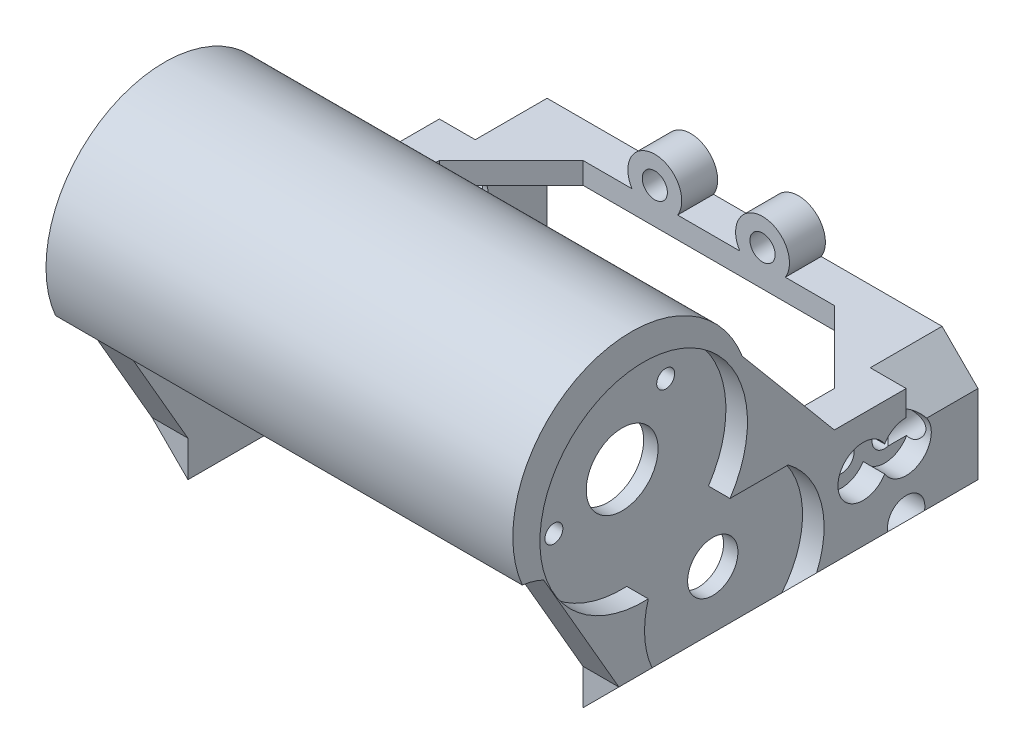
SolidWorks part; units mm, degrees
ref_plane "Front Plane" through (0, 0, 0) normal (0, 0, 1) x (1, 0, 0)
ref_plane "Top Plane" through (0, 0, 0) normal (0, 1, 0) x (1, 0, 0)
ref_plane "Right Plane" through (0, 0, 0) normal (1, 0, 0) x (0, 0, -1)
sketch "Sketch1" plane through (0, 0, 0) normal (1, 0, 0) x (0, 0, -1)
  line L0 (0, 0) -> (-11.1847, 15.9735) construction
  line L1 (0, 0) -> (24.1879, 0) construction
  line L3 (-3.4511, -28.0225) -> (46.5489, -28.0225)
  line L4 (46.5489, -28.0225) -> (46.5489, -7.0225)
  line L5 (26.5489, -7.0225) -> (46.5489, -7.0225)
  line L6 (-3.4511, -28.0225) -> (-3.4511, -23.0225)
  line L8 (6.0612, 7.9064) -> (-9.5027, -2.9915) construction
  line L9 (0, 0) -> (15.5119, -22.1533) construction
  line L10 (-3.4511, -23.0225) -> (-13.9311, -4.8707)
  line L11 (26.5489, -7.0225) -> (13.7066, 8.3096)
  line L12 (-3.4511, -23.0225) -> (-21.8299, -23.0225) construction
  arc A2 (-4.3527, -13.8313) -> (14.4859, -0.6404) centre (-1.7207, 2.4575) ccw construction
  circle A3 centre (0, 0) radius 5
  circle A4 centre (0, 0) radius 14.5 construction
  arc A6 (13.7066, 8.3096) -> (-16.9046, -4) centre (-1.7207, 2.4575) ccw
  circle A7 centre (6.0612, 7.9064) radius 1.25
  circle A8 centre (-9.5027, -2.9915) radius 1.25
  circle A9 centre (12.6187, -18.0213) radius 3.5
  circle A10 centre (36.5489, -14.0225) radius 1.75
  circle A11 centre (30.5489, -14.0225) radius 1.75
  circle A12 centre (36.5489, -22.5225) radius 2.6
  arc A13 (-16.9046, -4) -> (-13.9311, -4.8707) centre (-18.1939, -13.9165) cw
  point P13 (-15.6278, -4.8647)
  point P24 (-1.7207, 2.4575)
  point P32 (-15.9486, -4.3678)
  point P33 (-16.0428, -4.0182)
  dimension "D1" = 20
  dimension "D2" = 2.5
  dimension "D3" = 33
  dimension "D9" = 10
  dimension "D10" = 29
  dimension "D13" = 10
  dimension "D16" = 2.5
  dimension "D19" = 7
  dimension "D23" = 5.2
  dimension "D25" = 3.5
  dimension "D26" = 3.5
  dimension "D14" = 4
  dimension "D4" = 3
  dimension "D5" = 30.48
  dimension "D6" = 21
  dimension "D7" = 50
  dimension "D8" = 20
  dimension "D11" = 5
  dimension "D12" = 20.96
  dimension "D15" = 125
  dimension "D17" = 19
  dimension "D18" = 22
  dimension "D20" = 10
  dimension "D21" = 6
  dimension "D22" = 7
  dimension "D24" = 10
  dimension "D27" = 5.5
  dimension "D28" = 60
extrude "Boss-Extrude1" add sketch "Sketch1" along normal blind 5
sketch "Sketch2" plane through (5, 0, 0) normal (1, 0, 0) x (0, 0, -1)
  line L0 (9.1187, -30.0213) -> (16.1187, -30.0213)
  line L1 (20.1187, -8.0213) -> (12.0192, -8.0213)
  line L2 (-3.4511, -23.0225) -> (46.5489, -23.0225) construction
  line L3 (46.5489, -28.0225) -> (46.5489, -7.0225) construction
  arc A0 (12.0192, -8.0213) -> (0.644, -14.4356) centre (0, 0) ccw
  arc A1 (16.1187, -30.0213) -> (20.1187, -8.0213) centre (12.6187, -18.0213) ccw
  arc A2 (0.644, -14.4356) -> (9.1187, -30.0213) centre (12.6187, -18.0213) ccw
  arc A3 (33.5489, -15.8253) -> (33.5489, -12.2198) centre (36.5489, -14.0225) ccw
  arc A4 (33.5489, -12.2198) -> (33.5489, -15.8253) centre (30.5489, -14.0225) ccw
  dimension "D1" = 28.9
  dimension "D2" = 25
  dimension "D5" = 7
  dimension "D6" = 7
  dimension "D3" = 10
  dimension "D4" = 12
extrude "Cut-Extrude12" cut sketch "Sketch2" against normal blind 3
sketch "Sketch6" plane through (0, 0, -46.5489) normal (0, 0, -1) x (-1, 0, 0)
  line L0 (0, -28.0225) -> (-5, -23.0225)
  line L1 (-5, -28.0225) -> (-5, -7.0225) construction
  line L2 (-5, -23.0225) -> (-6.7772, -29.7998)
  line L3 (-6.7772, -29.7998) -> (0, -28.0225)
extrude "Cut-Extrude15" cut sketch "Sketch6" against normal up to next
sketch "Sketch7" plane through (5, 0, 0) normal (1, 0, 0) x (0, 0, -1)
  line L0 (-13.9311, -4.8707) -> (-13.6044, -4.8707)
  line L1 (13.7066, 8.3096) -> (12.3566, 7.4912)
  line L3 (46.5489, -7.0225) -> (41.5489, -7.0225)
  line L4 (46.5489, -7.0225) -> (46.5489, -10.0225)
  line L5 (46.5489, -10.0225) -> (41.5489, -10.0225)
  line L6 (41.5489, -7.0225) -> (41.5489, -10.0225)
  line L8 (39.1004, -23.0225) -> (46.5489, -23.0225)
  line L9 (46.5489, -23.0225) -> (46.5489, -7.0225)
  line L10 (46.5489, -7.0225) -> (26.5489, -7.0225)
  line L11 (26.5489, -7.0225) -> (13.7066, 8.3096)
  line L12 (-13.9311, -4.8707) -> (-3.4511, -23.0225)
  line L13 (-3.4511, -23.0225) -> (1.1628, -23.0225)
  line L14 (12.0192, -8.0213) -> (20.1187, -8.0213)
  line L15 (24.0746, -23.0225) -> (33.9974, -23.0225)
  arc A6 (13.7066, 8.3096) -> (-16.9046, -4) centre (-1.7207, 2.4575) ccw
  arc A7 (-13.9311, -4.8707) -> (-16.9046, -4) centre (-18.1939, -13.9165) ccw
  arc A8 (0.644, -14.4356) -> (1.1628, -23.0225) centre (12.6187, -18.0213) ccw
  arc A9 (12.0192, -8.0213) -> (0.644, -14.4356) centre (0, 0) ccw
  arc A10 (24.0746, -23.0225) -> (20.1187, -8.0213) centre (12.6187, -18.0213) ccw
  arc A11 (39.1004, -23.0225) -> (33.9974, -23.0225) centre (36.5489, -22.5225) ccw
  arc A12 (13.7066, 8.3096) -> (-16.9046, -4) centre (-1.7207, 2.4575) ccw
  arc A13 (-13.9311, -4.8707) -> (-16.9046, -4) centre (-18.1939, -13.9165) ccw
  arc A15 (12.3566, 7.4912) -> (-13.6044, -4.8707) centre (0, 0) ccw
  dimension "D2" = 5
  dimension "D3" = 3
  dimension "D1" = 0
extrude "Boss-Extrude2" add sketch "Sketch7" against normal blind 65
ref_plane "Plane2" through (-27.5, 0, 0) normal (1, 0, 0) x (0, 0, -1)
mirror "Mirror4" about plane through (-27.5, 0, 0) normal (1, 0, 0) of "Cut-Extrude15", "Cut-Extrude12", "Boss-Extrude1"
sketch "Sketch8" plane through (0, 0, -46.5489) normal (0, 0, -1) x (-1, 0, 0)
  line L0 (55, -28.0225) -> (55, -10.0225) construction
  line L1 (0, -28.0225) -> (0, -10.0225) construction
  line L2 (60, -7.0225) -> (55, -7.0225) construction
  line L3 (55, -7.0225) -> (60, -12.0225)
  line L4 (60, -23.0225) -> (60, -7.0225) construction
  line L5 (60, -12.0225) -> (62.6776, -4.345)
  line L6 (62.6776, -4.345) -> (55, -7.0225)
  line L7 (0, -7.0225) -> (-5, -12.0225)
  line L8 (-5, -23.0225) -> (-5, -7.0225) construction
  line L9 (-5, -12.0225) -> (-6.7771, -5.2455)
  line L10 (-6.7771, -5.2455) -> (0, -7.0225)
  circle A0 centre (-2.5, -14.0225) radius 1.75
  circle A1 centre (57.5, -14.0225) radius 1.75
  dimension "D1" = 3.5
  dimension "D2" = 3.5
  dimension "D3" = 2.5
  dimension "D4" = 2.5
  dimension "D5" = 7
extrude "Cut-Extrude16" cut sketch "Sketch8" against normal blind 10
sketch "Sketch10" plane through (0, 0, -46.5489) normal (0, 0, -1) x (-1, 0, 0)
  line L0 (0, -7.0225) -> (55, -7.0225) construction
  line L1 (0, -7.0225) -> (55, -7.0225) construction
  line L2 (35, -5.0225) -> (20, -5.0225) construction
  circle A0 centre (35, -5.0225) radius 3.75
  circle A1 centre (35, -5.0225) radius 1.75
  circle A2 centre (20, -5.0225) radius 3.75
  circle A3 centre (20, -5.0225) radius 1.75
  point P12 (27.5, -7.0225)
  point P13 (27.5, -5.0225)
  dimension "D2" = 7.5
  dimension "D3" = 3.5
  dimension "D1" = 15
  dimension "D4" = 2
extrude "Boss-Extrude3" add sketch "Sketch10" against normal blind 5
chamfer "Chamfer1" distance 10 angle 45 2 edges at (-55, -8.5225, -41.5489) (0, -8.5225, -41.5489)
